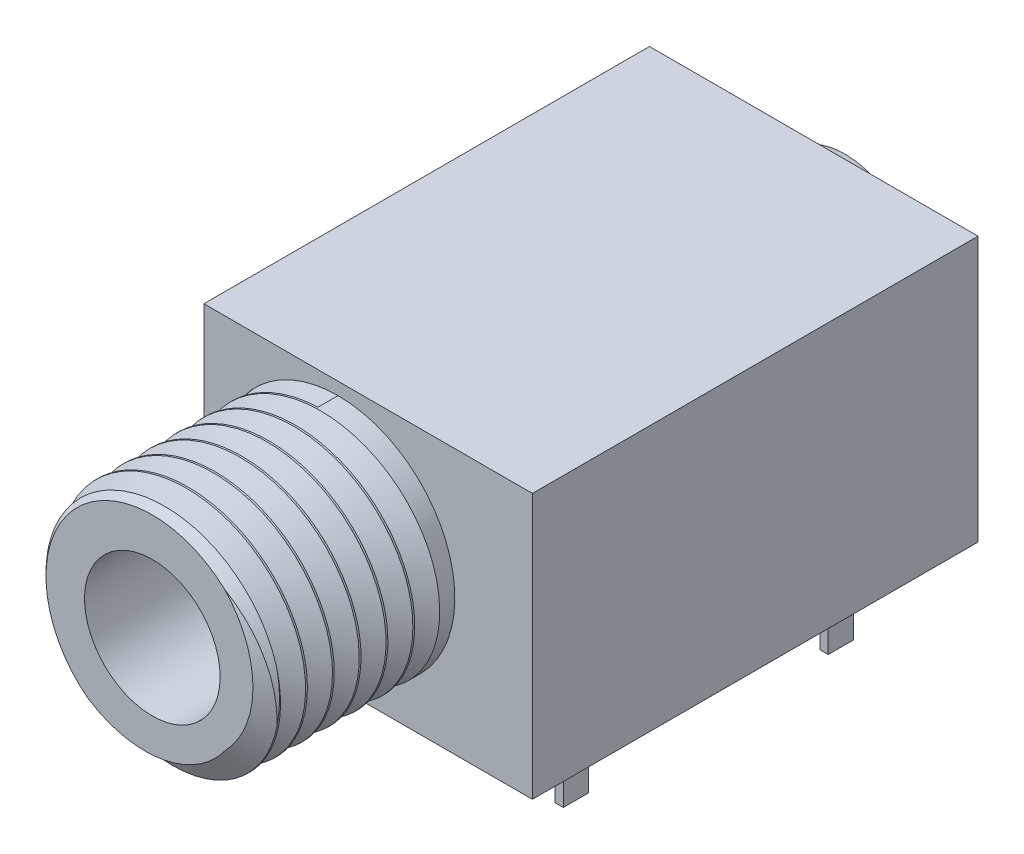
SolidWorks part; units mm, degrees
ref_plane "Front Plane" through (0, 0, 0) normal (0, 0, 1) x (1, 0, 0)
ref_plane "Top Plane" through (0, 0, 0) normal (0, 1, 0) x (1, 0, 0)
ref_plane "Right Plane" through (0, 0, 0) normal (1, 0, 0) x (0, 0, -1)
sketch "Sketch1" plane through (0, 0, 0) normal (0, 1, 0) x (1, 0, 0)
  line L1 (-14.6008, 12.6317) -> (1.1492, 12.6317)
  line L2 (-14.6008, 12.6317) -> (-14.6008, -8.7283)
  line L3 (-14.6008, -8.7283) -> (1.1492, -8.7283)
  line L4 (1.1492, 12.6317) -> (1.1492, -8.7283)
  dimension "D1" = 15.75
  dimension "D2" = 21.36
extrude "Boss-Extrude1" add sketch "Sketch1" along normal blind 12.7
sketch "Sketch3" plane through (0, 0, -12.6317) normal (0, 0, -1) x (-1, 0, 0)
  line L0 (-1.1492, 0) -> (14.6008, 0) construction
  line L1 (14.6008, 12.7) -> (14.6008, 0) construction
  circle A0 centre (8.1708, 6.5) radius 4
  point P6 (9.1995, 6.4563)
  dimension "D1" = 6.5
  dimension "D2" = 6.43
extrude "Boss-Extrude2" add sketch "Sketch3" along normal blind 2.94 draft 10
sketch "Sketch4" plane through (0, 0, 8.7283) normal (0, 0, 1) x (1, 0, 0)
  line L0 (-14.6008, 12.7) -> (-14.6008, 0) construction
  line L1 (-14.6008, 0) -> (1.1492, 0) construction
  circle A0 centre (-8.1708, 6.5) radius 5.6
  dimension "D1" = 6.43
  dimension "D2" = 6.5
extrude "Boss-Extrude3" add sketch "Sketch4" along normal blind 8.9
chamfer "Chamfer1" distance 0.5 angle 45 1 edges at (-2.5708, 6.5, 17.6283)
ref_plane "Plane1" through (0, 6.5, 0) normal (0, -1, 0) x (-1, 0, 0)
sketch "Sketch6" plane through (0, 6.5, 0) normal (0, -1, 0) x (-1, 0, 0)
  line L0 (13.7708, -16.5283) -> (13.7708, -17.7283)
  line L1 (13.7708, -17.1283) -> (13.7708, -8.7283) construction
  line L2 (2.5708, -17.1283) -> (13.7708, -17.1283) construction
  line L3 (13.7708, -17.7283) -> (12.7315, -17.1283)
  line L4 (12.7315, -17.1283) -> (13.7708, -16.5283)
  line L5 (8.1708, -18.6021) -> (8.1708, -10.6988) construction
  point P4 (13.7708, -17.1283)
  dimension "D1" = 5.6
  dimension "D3" = 1.2
sketch "Sketch9" plane through (0, 0, 17.6283) normal (0, 0, 1) x (1, 0, 0)
  circle A0 centre (-8.1708, 6.5) radius 5.6
curve "Helix/Spiral1" pitch 1.2857 height 9 radius 5.6 centre (-8.1708, 6.5, 17.6283) axis (0, 0, -1) start towards (0, 1, 0)
sweep "Cut-Sweep1" cut profiles "Sketch6" path "Helix/Spiral1"
sketch "Sketch13" plane through (0, 0, 17.6283) normal (0, 0, 1) x (1, 0, 0)
  circle A0 centre (-8.1708, 6.5) radius 3.25
  dimension "D1" = 6.5
extrude "Cut-Extrude1" cut sketch "Sketch13" against normal blind 29
sketch "Sketch14" plane through (0, 0, 0) normal (0, -1, 0) x (1, 0, 0)
  line L0 (-6.9358, -12.6317) -> (-6.9358, 8.7283) construction
  line L1 (-12.8508, 5.0783) -> (-12.4508, 5.0783)
  line L2 (-12.8508, 5.0783) -> (-12.8508, 3.8783)
  line L3 (-12.8508, 3.8783) -> (-12.4508, 3.8783)
  line L4 (-12.4508, 5.0783) -> (-12.4508, 3.8783)
  line L5 (-12.4508, -7.6217) -> (-12.4508, -8.8217)
  line L6 (-8.2508, -1.3881) -> (-8.2508, 3.8102) construction
  line L7 (-12.8508, -7.6217) -> (-12.8508, -8.8217)
  line L8 (-12.8508, -8.8217) -> (-12.4508, -8.8217)
  line L9 (-12.8508, -7.6217) -> (-12.4508, -7.6217)
  line L10 (-1.0208, -8.8217) -> (-1.4208, -8.8217)
  line L11 (-1.0208, 3.8783) -> (-1.4208, 3.8783)
  line L12 (-1.0208, 5.0783) -> (-1.0208, 3.8783)
  line L13 (-1.4208, 5.0783) -> (-1.4208, 3.8783)
  line L14 (-1.0208, 5.0783) -> (-1.4208, 5.0783)
  line L15 (-1.0208, -7.6217) -> (-1.0208, -8.8217)
  line L16 (-1.0208, -7.6217) -> (-1.4208, -7.6217)
  line L17 (-14.6008, -12.6317) -> (-14.6008, 8.7283) construction
  line L18 (-14.6008, 8.7283) -> (1.1492, 8.7283) construction
  line L19 (-1.4208, -7.6217) -> (-1.4208, -8.8217)
  dimension "D1" = 1.2
  dimension "D2" = 0.4
  dimension "D3" = 2
  dimension "D4" = 5.515
  dimension "D5" = 6.35
  dimension "D6" = 4.2
  dimension "D7" = 3.65
extrude "Boss-Extrude4" add sketch "Sketch14" along normal blind 3.25
